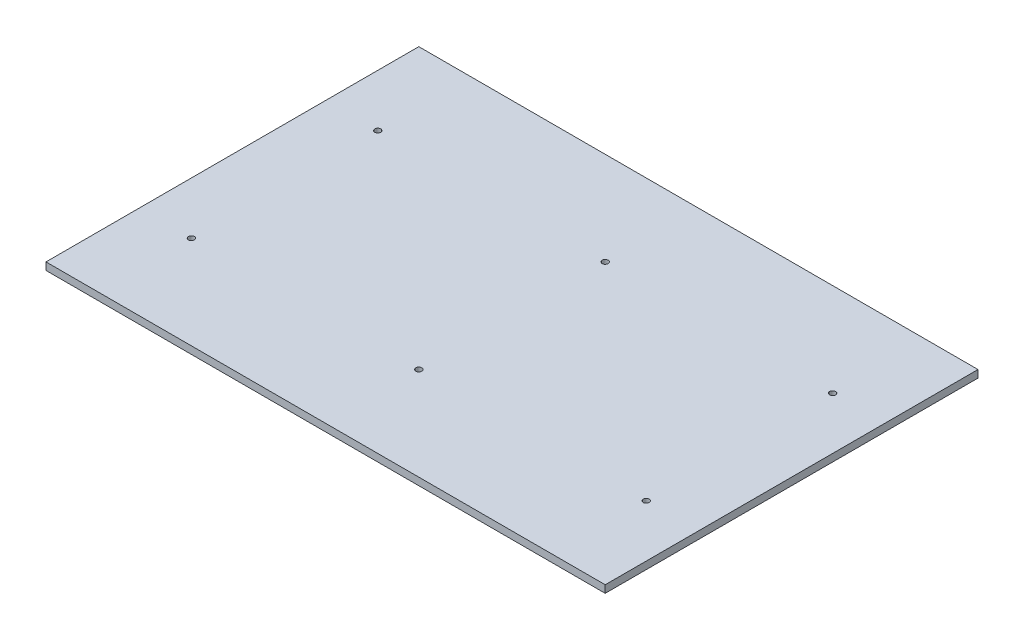
SolidWorks part; units mm, degrees
material "Stainless Steel (ferritic)"
ref_plane "Front Plane" through (0, 0, 0) normal (0, 0, 1) x (1, 0, 0)
ref_plane "Top Plane" through (0, 0, 0) normal (0, 1, 0) x (1, 0, 0)
ref_plane "Right Plane" through (0, 0, 0) normal (1, 0, 0) x (0, 0, -1)
sketch "Sketch1" plane through (0, 0, 0) normal (0, 1, 0) x (1, 0, 0)
  line L1 (-375, 250) -> (375, 250)
  line L2 (-375, 250) -> (-375, -250)
  line L3 (-375, -250) -> (375, -250)
  line L4 (375, 250) -> (375, -250)
  line L5 (-375, 250) -> (375, -250) construction
  line L6 (-375, -250) -> (375, 250) construction
  point P0 (0, 0)
extrude "Boss-Extrude1" add sketch "Sketch1" along normal blind 10
sketch "Sketch2" plane through (0, 10, 0) normal (0, 1, 0) x (1, 0, 0)
  line L0 (375, 250) -> (-375, 250) construction
  line L1 (375, -250) -> (375, 250) construction
  circle A0 centre (305, 125) radius 4
  point P2 (0, 0)
  dimension "D1" = 125
  dimension "D2" = 70
  dimension "D3" = 8
extrude "Cut-Extrude1" cut sketch "Sketch2" against normal blind 10
sketch "Sketch3" plane through (0, 10, 0) normal (0, 1, 0) x (1, 0, 0)
  line L0 (-375, -250) -> (375, -250) construction
  line L1 (375, -250) -> (375, 250) construction
  circle A0 centre (305, -125) radius 4
  dimension "D1" = 125
  dimension "D2" = 70
  dimension "D3" = 8
extrude "Cut-Extrude2" cut sketch "Sketch3" against normal blind 10
sketch "Sketch4" plane through (0, 10, 0) normal (0, 1, 0) x (1, 0, 0)
  line L0 (375, -250) -> (375, 250) construction
  line L1 (375, 250) -> (-375, 250) construction
  circle A0 centre (0, 125) radius 4
  dimension "D1" = 8
  dimension "D2" = 375
  dimension "D3" = 125
extrude "Cut-Extrude3" cut sketch "Sketch4" against normal blind 10
sketch "Sketch5" plane through (0, 10, 0) normal (0, 1, 0) x (1, 0, 0)
  circle A0 centre (0, -125) radius 4
extrude "Cut-Extrude4" cut sketch "Sketch5" against normal blind 10
sketch "Sketch6" plane through (0, 10, 0) normal (0, 1, 0) x (1, 0, 0)
  line L0 (-375, 250) -> (-375, -250) construction
  line L1 (375, 250) -> (-375, 250) construction
  circle A0 centre (-305, 125) radius 4
  dimension "D1" = 70
  dimension "D2" = 125
  dimension "D3" = 8
extrude "Cut-Extrude5" cut sketch "Sketch6" against normal blind 10
sketch "Sketch7" plane through (0, 10, 0) normal (0, 1, 0) x (1, 0, 0)
  line L0 (-375, 250) -> (-375, -250) construction
  line L1 (-375, -250) -> (375, -250) construction
  circle A0 centre (-305, -125) radius 4
  dimension "D1" = 8
  dimension "D2" = 70
  dimension "D3" = 125
extrude "Cut-Extrude6" cut sketch "Sketch7" against normal blind 10 contours A0
sketch "Sketch9" plane through (0, 10, 0) normal (0, 1, 0) x (1, 0, 0)
  line L0 (-375, 250) -> (0, 250) construction
  line L1 (375, 250) -> (-375, 250) construction
  line L2 (-187.5, 250) -> (-187.5, -250) construction
  line L3 (-375, -250) -> (375, -250) construction
